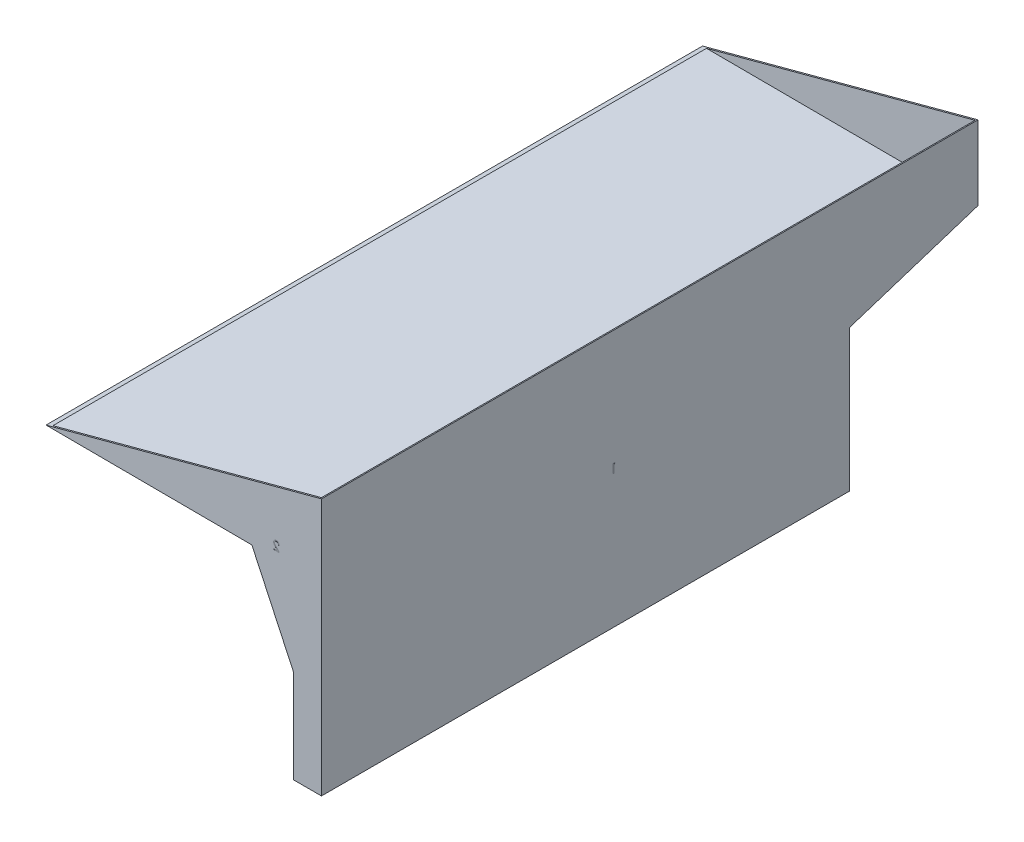
SolidWorks part; units mm, degrees
material "Melamine"
ref_plane "Front Plane" through (0, 0, 0) normal (0, 0, 1) x (1, 0, 0)
ref_plane "Top Plane" through (0, 0, 0) normal (0, 1, 0) x (1, 0, 0)
ref_plane "Right Plane" through (0, 0, 0) normal (1, 0, 0) x (0, 0, -1)
other "Center of Mass"
sketch "Sketch2" plane through (0, 0, 0) normal (0, 0, 1) x (1, 0, 0)
  line L0 (0, 0) -> (-88.7498, 190.3246)
  line L1 (-88.7498, 190.3246) -> (-528.8284, 192.2239)
  line L2 (-528.8284, 192.2239) -> (60, 350)
  line L3 (60, 350) -> (60, -200)
  line L4 (60, -200) -> (0, -200)
  line L5 (0, -200) -> (0, 0)
  dimension "D1" = 155
  dimension "D2" = 609.6
  dimension "D3" = 550
  dimension "D4" = 200
  dimension "D5" = 60
  dimension "D6" = 210
  dimension "D7" = 285
extrude "Boss-Extrude1" add sketch "Sketch2" along normal mid plane 1403.35
shell "Shell1" thickness 3.175 removed face at (-234.4142, 271.112, 0)
sketch "Sketch3" plane through (0, 0, 701.675) normal (0, 0, 1) x (1, 0, 0)
  line L1 (9, -187.3) -> (51, -187.3)
  line L2 (9, -187.3) -> (9, 102.7)
  line L3 (9, 102.7) -> (51, 102.7)
  line L4 (51, -187.3) -> (51, 102.7)
  line L6 (0, -200) -> (60, -200) construction
  point P6 (30, -200)
  point P7 (30, -187.3)
  dimension "D1" = 42
  dimension "D2" = 12.7
  dimension "D3" = 290
extrude "Cut-Extrude1" cut sketch "Sketch3" against normal blind 20
sketch "Sketch7" plane through (0, 0, 0) normal (-1, 0, 0) x (0, 0, 1)
  line L1 (701.675, -200) -> (426.675, -200)
  line L2 (701.675, -200) -> (701.675, 102.7)
  line L3 (701.675, 102.7) -> (426.675, 102.7)
  line L4 (426.675, -200) -> (426.675, 102.7)
  dimension "D1" = 275
  dimension "D2" = 302.7
extrude "Cut-Extrude5" cut sketch "Sketch7" against normal mid plane 200
sketch "Sketch9" plane through (60, 0, 0) normal (1, 0, 0) x (0, 0, -1)
  line L1 (-426.675, 102.7) -> (-701.675, 102.7)
  line L2 (-426.675, 102.7) -> (-426.675, 191.216)
  line L3 (-426.675, 191.216) -> (-701.675, 191.216)
  line L4 (-701.675, 102.7) -> (-701.675, 191.216)
  line L5 (-701.675, 191.216) -> (-426.675, 102.7)
  line M2 (-701.675, 102.7) -> (-426.675, 102.7)
  line M7 (-701.675, 350) -> (-701.675, 102.7)
  dimension "D1" = 88.516
extrude "Cut-Extrude7" cut sketch "Sketch9" against normal up to vertex (148.7498 mm away) contours L5 M7 M2 region at (60, 132.2053, 610.0083) up to point (-88.7498, 190.3246, 701.675)
sketch "Sketch11" plane through (0, -31.385, 10.1021) normal (0, -0.9519, 0.3064) x (1, 0, 0)
  line L0 (60, 726.5152) -> (60, 437.6206)
  line L1 (60, 437.6206) -> (-47.8898, 437.6206)
  line L2 (-47.8898, 437.6206) -> (-86.0836, 726.5152)
  line L3 (-86.0836, 726.5152) -> (60, 726.5152)
  line L4 (-88.7498, 726.5152) -> (60, 726.5152) construction
extrude "Boss-Extrude3" add sketch "Sketch11" against normal blind 3.175
sketch "Sketch12" plane through (3.175, 0, 0) normal (1, 0, 0) x (0, 0, -1)
  line L0 (-426.675, -196.825) -> (688.975, -79.5655)
  line L1 (688.975, -79.5655) -> (688.975, -82.7405)
  line L2 (-396.4669, -196.825) -> (-426.675, -196.825)
  line L3 (701.675, -200) -> (701.675, 350) construction
  line L4 (688.975, -82.7405) -> (-396.4669, -196.825)
  line L5 (-396.4669, -196.825) -> (-396.4669, -193.65)
  line M5 (-426.675, -196.825) -> (698.5, -196.825)
  dimension "D1" = 3.175
  dimension "D2" = 12.7
  dimension "D3" = 6
  dimension "D4" = 3.175
  dimension "D5" = 3.175
extrude "Boss-Extrude4" add sketch "Sketch12" along normal up to surface (53.65 mm away) contours L5 L4 L1 L0 | L5 L0 M5 region at (3.175, -195.7667, 406.5363) region at (3.175, -138.1952, -146.2541) up to face at (56.825, 100.9429, 182.7217)
chamfer "Chamfer1" distance 6.35 angle 45 1 edges at (30, -196.825, 426.675) first distance on face at (30, -138.1952, -131.15)
sketch "Sketch14" plane through (60, 0, 0) normal (1, 0, 0) x (0, 0, -1)
  line L0 (-426.675, 102.7) -> (-426.675, -200) construction
  line L1 (-426.675, -200) -> (701.675, -200) construction
  text T0 "1" font "Century Gothic" height in points 72
  dimension "D1" = 496.5296
  dimension "D2" = 284.9328
extrude "Cut-Extrude8" cut sketch "Sketch14" against normal blind 0.1
sketch "Sketch15" plane through (0, 0, -701.675) normal (0, 0, -1) x (-1, 0, 0)
  text T0 "2" font "Century Gothic" height in points 72
extrude "Cut-Extrude9" cut sketch "Sketch15" against normal blind 0.1
sketch "Sketch16" plane through (0.8197, 189.9381, 0) normal (-0.0043, -1, 0) x (1, -0.0043, 0)
  text T0 "3" font "Century Gothic" height in points 72
extrude "Cut-Extrude10" cut sketch "Sketch16" against normal blind 0.1
sketch "Sketch17" plane through (0, 0, 0) normal (-0.9063, -0.4226, 0) x (0, 0, 1)
  text T0 "4" font "Century Gothic" height in points 72
extrude "Cut-Extrude11" cut sketch "Sketch17" against normal blind 0.1
sketch "Sketch18" plane through (0, 0, 0) normal (-1, 0, 0) x (0, 0, 1)
  text T0 "5" font "Century Gothic" height in points 72
extrude "Cut-Extrude12" cut sketch "Sketch18" against normal blind 0.1
sketch "Sketch19" plane through (0, -200, 0) normal (0, -1, 0) x (1, 0, 0)
  text T0 "6" font "Century Gothic" height in points 72
extrude "Cut-Extrude13" cut sketch "Sketch19" against normal blind 0.1
sketch "Sketch20" plane through (0, -31.385, 10.1021) normal (0, -0.9519, 0.3064) x (1, 0, 0)
  text T0 "7" font "Century Gothic" height in points 72
extrude "Cut-Extrude14" cut sketch "Sketch20" against normal blind 0.1
sketch "Sketch21" plane through (0, 0, 701.675) normal (0, 0, 1) x (1, 0, 0)
  text T0 "8" font "Century Gothic" height in points 72
extrude "Cut-Extrude15" cut sketch "Sketch21" against normal blind 0.1
mirror "Mirror1" about plane through (0, 0, -701.675) normal (0, 0, 1) of bodies 122
sketch "Sketch22" plane through (0, 0, 0) normal (-1, 0, 0) x (0, 0, 1)
  line L5 (-701.675, -200) -> (1024.7166, -200)
  line L6 (-701.675, -200) -> (-701.675, 602.0407)
  line L7 (-701.675, 602.0407) -> (1024.7166, 602.0407)
  line L8 (1024.7166, -200) -> (1024.7166, 602.0407)
extrude "Cut-Extrude16" cut sketch "Sketch22" against normal through all both and the other way through all
